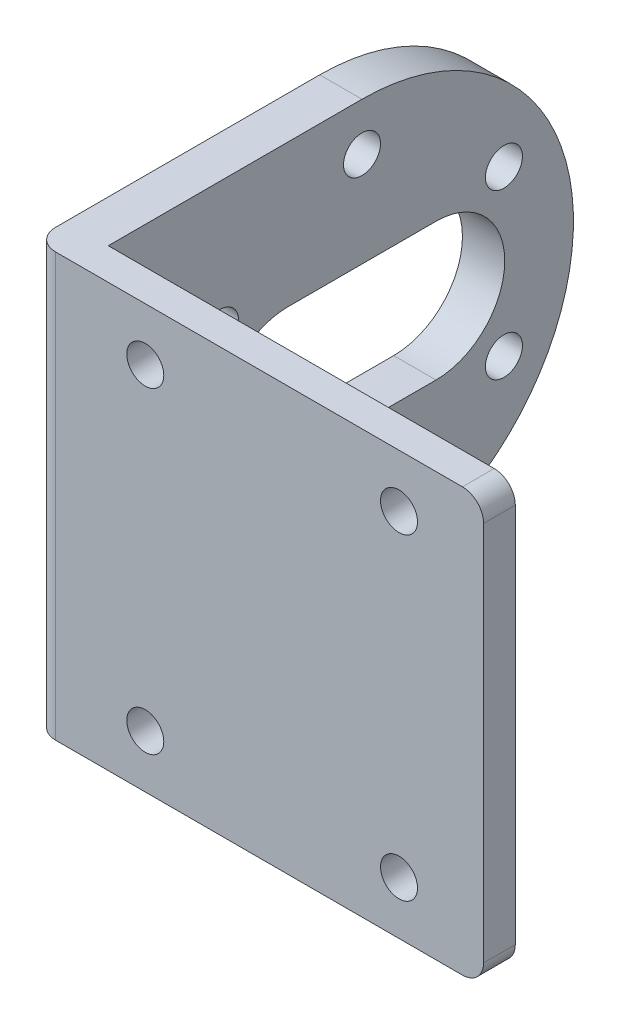
SolidWorks part; units mm, degrees
ref_plane "Front Plane" through (0, 0, 0) normal (0, 0, 1) x (1, 0, 0)
ref_plane "Top Plane" through (0, 0, 0) normal (0, 1, 0) x (1, 0, 0)
ref_plane "Right Plane" through (0, 0, 0) normal (1, 0, 0) x (0, 0, -1)
sketch "Sketch1" plane through (0, 0, 0) normal (0, 1, 0) x (1, 0, 0)
  line L0 (0, 0) -> (0, 27)
  line L1 (0, 27) -> (3, 27)
  line L2 (3, 27) -> (3, 3)
  line L3 (3, 3) -> (42.5, 3)
  line L4 (42.5, 3) -> (42.5, 0)
  line L5 (42.5, 0) -> (0, 0)
  dimension "D1" = 27
  dimension "D2" = 3
  dimension "D3" = 3
  dimension "D4" = 42.5
extrude "Boss-Extrude1" add sketch "Sketch1" along normal blind 40
sketch "Sketch2" plane through (3, 0, 0) normal (1, 0, 0) x (0, 0, -1)
  line L4 (3, 0) -> (27, 0) construction
  line L5 (3, 40) -> (27, 40) construction
  line L11 (3, 0) -> (27, 0)
  line L12 (27, 0) -> (27, 40)
  line L13 (27, 40) -> (3, 40)
  line L14 (3, 40) -> (3, 0)
  line L15 (3, 0) -> (27, 0)
  line L17 (27, 40) -> (3, 40)
  line L18 (3, 40) -> (3, 0)
  arc A0 (27, 40) -> (27, 0) centre (27, 20) cw
  dimension "D1" = 0
extrude "Boss-Extrude2" add sketch "Sketch2" along normal blind 1 and the other way blind 3
sketch "Sketch3" plane through (4, 0, 0) normal (1, 0, 0) x (0, 0, -1)
  line L0 (27, 40) -> (3, 40) construction
  line L1 (20, 26.5) -> (34, 26.5)
  line L3 (20, 13.5) -> (34, 13.5)
  line L5 (20, 26.5) -> (27, 20) construction
  line L6 (27, 20) -> (34, 26.5) construction
  arc A0 (34, 26.5) -> (34, 13.5) centre (34, 20) cw
  arc A1 (20, 26.5) -> (20, 13.5) centre (20, 20) ccw
  point P0 (27, 20)
  dimension "D1" = 14
  dimension "D2" = 13
  dimension "D3" = 13.5
extrude "Cut-Extrude1" cut sketch "Sketch3" against normal through all
sketch "Sketch4" plane through (4, 0, 0) normal (1, 0, 0) x (0, 0, -1)
  line L0 (0, 40) -> (0, 0) construction
  circle A0 centre (27, 20) radius 15.5 construction
  dimension "D1" = 31
  dimension "D2" = 27
sketch "Sketch5" plane through (4, 0, 0) normal (1, 0, 0) x (0, 0, -1)
  circle A2 centre (27, 4.5) radius 1.75
  circle A3 centre (27, 20) radius 15.5 construction
  circle A4 centre (13.5766, 12.25) radius 1.75
  circle A5 centre (13.5766, 27.75) radius 1.75
  circle A6 centre (27, 35.5) radius 1.75
  circle A7 centre (40.4234, 27.75) radius 1.75
  circle A8 centre (40.4234, 12.25) radius 1.75
  point P17 (27, 20)
  dimension "D1" = 3.5
  dimension "D2" = 6
extrude "Cut-Extrude2" cut sketch "Sketch5" against normal through all
fillet "Fillet1" radius 2 3 edges at (42.5, 40, -1.5) (42.5, 0, -1.5) (0, 20, 0)
sketch "Sketch6" plane through (0, 0, 0) normal (0, 0, 1) x (1, 0, 0)
  line L0 (42.5, 38) -> (42.5, 2) construction
  line L1 (2, 0) -> (40.5, 0) construction
  circle A0 centre (34.5, 5) radius 1.75
  circle A1 centre (34.5, 35) radius 1.75
  circle A2 centre (10.5, 35) radius 1.75
  circle A3 centre (10.5, 5) radius 1.75
  point P7 (0, 0)
  dimension "D1" = 3.5
  dimension "D2" = 8
  dimension "D3" = 5
  dimension "D5" = 30
  dimension "D6" = 24
  dimension "D4" = 2
extrude "Cut-Extrude3" cut sketch "Sketch6" against normal up to next
